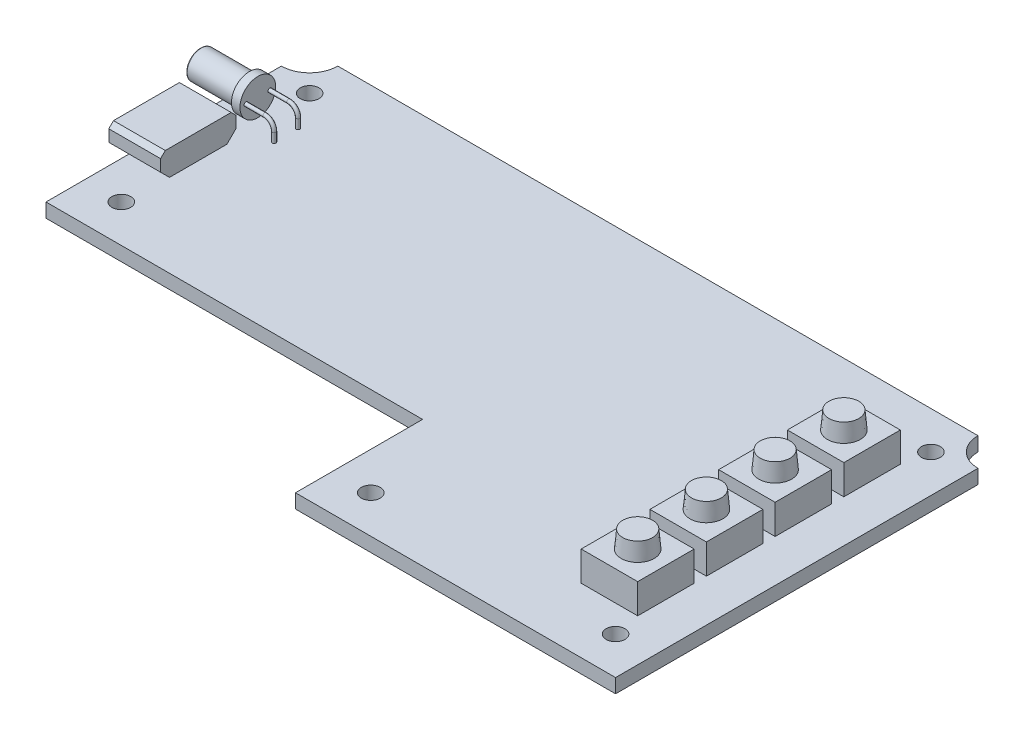
SolidWorks part; units mm, degrees
ref_plane "Front" through (0, 0, 0) normal (0, 0, 1) x (1, 0, 0)
ref_plane "Top" through (0, 0, 0) normal (0, 1, 0) x (1, 0, 0)
ref_plane "Right" through (0, 0, 0) normal (1, 0, 0) x (0, 0, -1)
sketch "Эскиз1" plane through (0, 0, 0) normal (0, 1, 0) x (1, 0, 0)
  line L0 (-37, -9) -> (3, -9)
  line L1 (37, -22.5) -> (-37, -22.5) construction
  line L2 (37, -22.5) -> (37, 19) construction
  line L3 (37, 19) -> (-37, 19) construction
  line L4 (-37, -22.5) -> (-37, 19) construction
  line L5 (0, -1.75) -> (0, 0) construction
  line L6 (-33, -18.5) -> (33, -18.5) construction
  line L7 (-33, -18.5) -> (-33, 15) construction
  line L8 (-33, 15) -> (33, 15) construction
  line L9 (33, -18.5) -> (33, 15) construction
  line L10 (-33, -18.5) -> (33, 15) construction
  line L11 (-33, 15) -> (33, -18.5) construction
  line L18 (37, -22.5) -> (-37, 19) construction
  line L19 (37, 19) -> (-37, -22.5) construction
  line L20 (3, -9) -> (3, -22.5)
  line L21 (-37, 19) -> (-37, -9) construction
  line L22 (3, -22.5) -> (37, -22.5)
  line L23 (37, -22.5) -> (37, 16)
  line L24 (34, 19) -> (-34, 19)
  line L25 (-37, 16) -> (-37, -9)
  line L26 (37, 19) -> (37, -22.5) construction
  line L27 (37, 19) -> (-37, 19) construction
  line L28 (-37, 19) -> (-37, -22.5) construction
  circle A0 centre (-33, -18.5) radius 1 construction
  circle A1 centre (-33, -5) radius 1
  circle A2 centre (33, -18.5) radius 1
  circle A3 centre (7, -18.5) radius 1
  circle A4 centre (-33, 15) radius 1
  arc A5 (-37, 16) -> (-34, 19) centre (-37, 19) ccw
  circle A6 centre (33, 15) radius 1
  arc A7 (37, 16) -> (34, 19) centre (37, 19) cw
  point P7 (0, -1.75)
  dimension "D4" = 74
  dimension "D5" = 41.5
  dimension "D6" = 28
  dimension "D7" = 40
  dimension "D9" = 2
  dimension "D10" = 3
  dimension "D11" = 3
  dimension "D1" = 1.75
  dimension "D2" = 33.5
  dimension "D3" = 66
  dimension "D8" = 20
  dimension "D12" = 26
extrude "Бобышка-Вытянуть1" add sketch "Эскиз1" along normal blind 1.5
sketch "Эскиз2" plane through (0, 1.5, 0) normal (0, 1, 0) x (1, 0, 0)
  line L1 (26.5, 11.5) -> (32.5, 11.5) construction
  line L2 (26.5, 11.5) -> (26.5, 7) construction
  line L3 (26.5, 7) -> (32.5, 7) construction
  line L4 (32.5, 11.5) -> (32.5, 7) construction
  line L5 (26.5, 11.5) -> (32.5, 7) construction
  line L6 (26.5, 7) -> (32.5, 11.5) construction
  line L8 (26.5, 4.2) -> (26.5, -0.3) construction
  line L9 (26.5, 4.2) -> (32.5, 4.2) construction
  line L10 (32.5, 4.2) -> (32.5, -0.3) construction
  line L11 (26.5, -0.3) -> (32.5, -0.3) construction
  line L12 (26.5, 4.2) -> (32.5, -0.3) construction
  line L13 (26.5, -0.3) -> (32.5, 4.2) construction
  line L14 (26.5, -3.1) -> (26.5, -7.6) construction
  line L15 (26.5, -3.1) -> (32.5, -3.1) construction
  line L16 (32.5, -3.1) -> (32.5, -7.6) construction
  line L17 (26.5, -7.6) -> (32.5, -7.6) construction
  line L18 (26.5, -3.1) -> (32.5, -7.6) construction
  line L19 (26.5, -7.6) -> (32.5, -3.1) construction
  line L20 (26.5, -10.4) -> (26.5, -14.9) construction
  line L21 (26.5, -10.4) -> (32.5, -10.4) construction
  line L22 (32.5, -10.4) -> (32.5, -14.9) construction
  line L23 (26.5, -14.9) -> (32.5, -14.9) construction
  line L24 (26.5, -10.4) -> (32.5, -14.9) construction
  line L25 (26.5, -14.9) -> (32.5, -10.4) construction
  line L26 (32.5, 4.95) -> (32.5, -1.05)
  line L27 (32.5, 12.25) -> (26.5, 12.25)
  line L28 (32.5, 12.25) -> (32.5, 6.25)
  line L29 (32.5, 6.25) -> (26.5, 6.25)
  line L30 (26.5, 12.25) -> (26.5, 6.25)
  line L31 (32.5, 12.25) -> (26.5, 6.25) construction
  line L32 (32.5, 6.25) -> (26.5, 12.25) construction
  line L33 (32.5, 4.95) -> (26.5, 4.95)
  line L34 (26.5, 4.95) -> (26.5, -1.05)
  line L35 (32.5, -1.05) -> (26.5, -1.05)
  line L36 (32.5, -2.35) -> (32.5, -8.35)
  line L37 (32.5, -2.35) -> (26.5, -2.35)
  line L38 (26.5, -2.35) -> (26.5, -8.35)
  line L39 (32.5, -8.35) -> (26.5, -8.35)
  line L40 (32.5, -9.65) -> (32.5, -15.65)
  line L41 (32.5, -9.65) -> (26.5, -9.65)
  line L42 (26.5, -9.65) -> (26.5, -15.65)
  line L43 (32.5, -15.65) -> (26.5, -15.65)
  line L44 (34, 19) -> (37, 19) construction
  line L45 (37, 19) -> (37, 16) construction
  line L46 (37, -22.5) -> (37, 16) construction
  line L47 (34, 19) -> (-34, 19) construction
  point P0 (29.5, 9.25)
  point P9 (29.5, 9.25)
  dimension "D1" = 4.5
  dimension "D2" = 6
  dimension "D3" = 7.5
  dimension "D4" = 4.5
  dimension "D6" = 6
  dimension "D7" = 6
  dimension "D8" = 4
  dimension "D5" = 4
extrude "Бобышка-Вытянуть2" add sketch "Эскиз2" along normal blind 3.15
sketch "Эскиз3" plane through (0, 4.65, 0) normal (0, 1, 0) x (1, 0, 0)
  line L0 (26.5, 12.25) -> (32.5, 6.25) construction
  line L1 (26.5, 4.95) -> (32.5, -1.05) construction
  line L2 (32.5, 12.25) -> (26.5, 6.25) construction
  line L3 (26.5, 4.95) -> (26.5, -1.05) construction
  line L4 (32.5, 4.95) -> (26.5, -1.05) construction
  line L5 (26.5, 4.95) -> (26.5, -1.05) construction
  line L6 (32.5, -8.35) -> (26.5, -2.35) construction
  line L7 (32.5, -2.35) -> (26.5, -8.35) construction
  line L8 (32.5, -2.35) -> (26.5, -2.35) construction
  line L9 (26.5, -2.35) -> (26.5, -8.35) construction
  line L10 (26.5, -9.65) -> (32.5, -15.65) construction
  line L11 (32.5, -9.65) -> (26.5, -15.65) construction
  circle A0 centre (29.5, 9.25) radius 1.75
  circle A1 centre (29.5, 1.95) radius 1.75
  circle A2 centre (29.5, -5.35) radius 1.75
  circle A3 centre (29.5, -12.65) radius 1.75
  dimension "D1" = 3.5
extrude "Бобышка-Вытянуть3" add sketch "Эскиз3" along normal blind 1.85 draft 5
sketch "Эскиз4" plane through (0, 1.5, 0) normal (0, 1, 0) x (1, 0, 0)
  line L0 (-27.2061, 19) -> (-27.2061, 2.87) construction
  line L2 (-27.2061, 2.87) -> (-37, 2.87) construction
  line L4 (-37, 16) -> (-37, 19) construction
  line L5 (-32.7, -1.13) -> (-38.2, -1.13)
  line L6 (-32.7, -1.13) -> (-32.7, 6.87)
  line L7 (-32.7, 6.87) -> (-38.2, 6.87)
  line L8 (-38.2, -1.13) -> (-38.2, 6.87)
  line L9 (-32.7, -1.13) -> (-38.2, 6.87) construction
  line L10 (-32.7, 6.87) -> (-38.2, -1.13) construction
  line L11 (-37, 19) -> (-34, 19) construction
  line L12 (-37, 16) -> (-37, -9) construction
  line L13 (34, 19) -> (-34, 19) construction
  point P4 (-35.45, 2.87)
  dimension "D1" = 16.13
  dimension "D2" = 1.2
  dimension "D3" = 5.5
  dimension "D4" = 8
extrude "Бобышка-Вытянуть4" add sketch "Эскиз4" along normal blind 2.4
sketch "Эскиз5" plane through (-38.2, 0, 0) normal (-1, 0, 0) x (0, 0, 1)
  line L0 (-6.87, 3.9) -> (1.13, 1.5) construction
  line L1 (1.13, 3.9) -> (1.13, 1.5) construction
  line L2 (-6.87, 1.5) -> (1.13, 1.5) construction
  line L3 (-6.87, 1.5) -> (1.13, 3.9) construction
  line L4 (-6.87, 3.9) -> (-6.87, 1.5) construction
  line L6 (1.13, 1.2) -> (-6.87, 1.2)
  line L7 (1.13, 1.2) -> (1.13, 4.2)
  line L8 (1.13, 4.2) -> (-6.87, 4.2)
  line L9 (-6.87, 1.2) -> (-6.87, 4.2)
  line L10 (1.13, 1.2) -> (-6.87, 4.2) construction
  line L11 (1.13, 4.2) -> (-6.87, 1.2) construction
  point P12 (-2.87, 2.7)
  dimension "D1" = 3
extrude "Бобышка-Вытянуть5" add sketch "Эскиз5" against normal up to surface (5.5 mm away) up to face at (-32.7, 2.7, -2.87)
chamfer "Фаска1" distance 0.5 angle 45 2 edges at (-35.45, 4.2, -6.87) (-35.45, 4.2, 1.13)
chamfer "Фаска2" distance 1.25 2 edges at (-37.6, 1.2, 1.13) (-37.6, 1.2, -6.87)
sketch "Эскиз6" plane through (0, 1.5, 0) normal (0, 1, 0) x (1, 0, 0)
  line L0 (-30.4, 19) -> (-30.4, 11.17) construction
  line L2 (-30.4, 11.17) -> (-37, 11.17) construction
  line L4 (-30.4, 11.17) -> (-30.4, 8.63) construction
  line L5 (34, 19) -> (-34, 19) construction
  line L6 (-37, 16) -> (-37, 5.92) construction
  circle A0 centre (-30.4, 11.17) radius 0.2
  circle A1 centre (-30.4, 8.63) radius 0.2
  dimension "D3" = 0.4
  dimension "D1" = 7.83
  dimension "D2" = 6.6
  dimension "D4" = 2.54
sketch "Эскиз7" plane through (0, 0, 0) normal (0, 0, 1) x (1, 0, 0)
  line L0 (-30.4, 1.5) -> (-30.4, 2.5)
  line L1 (-30.4, 1.5) -> (-37, 1.5) construction
  line L2 (-33.4, 3.5) -> (-31.4, 3.5)
  arc A0 (-30.4, 2.5) -> (-31.4, 3.5) centre (-31.4, 2.5) ccw
  dimension "D1" = 1
  dimension "D2" = 2
  dimension "D3" = 2
sweep "По траектории1" add profiles "Эскиз6" path "Эскиз7"
sketch "Эскиз8" plane through (-33.4, 0, 0) normal (-1, 0, 0) x (0, 0, 1)
  line L0 (-11.37, 3.5) -> (-8.43, 3.5) construction
  circle A0 centre (-9.9, 3.5) radius 1.9
  dimension "D1" = 3.8
extrude "Бобышка-Вытянуть6" add sketch "Эскиз8" along normal blind 0.9
sketch "Эскиз9" plane through (-34.3, 0, 0) normal (-1, 0, 0) x (0, 0, 1)
  line L0 (-16, 0) -> (9, 0) construction
  line L2 (-19, 1.5) -> (-19, 0) construction
  circle A0 centre (-9.9, 3.5) radius 1.5
  circle A1 centre (-9.9, 3.5) radius 1.9 construction
  dimension "D1" = 3
  dimension "D2" = 3.5
  dimension "D3" = 9.1
extrude "Бобышка-Вытянуть7" add sketch "Эскиз9" along normal blind 5.2
sketch "Эскиз16" plane through (-38.2, 0, 0) normal (-1, 0, 0) x (0, 0, 1)
  line L0 (-6.67, 3.6172) -> (-6.67, 2.5328)
  line L1 (-6.67, 2.5328) -> (-5.5372, 1.4)
  line L2 (-5.5372, 1.4) -> (-0.2028, 1.4)
  line L3 (-0.2028, 1.4) -> (0.93, 2.5328)
  line L4 (0.93, 2.5328) -> (0.93, 3.6172)
  line L5 (0.93, 3.6172) -> (0.5472, 4)
  line L6 (0.5472, 4) -> (-6.2872, 4)
  line L7 (-6.2872, 4) -> (-6.67, 3.6172)
  line L8 (-6.37, 4.2) -> (-6.87, 3.7) construction
  line L9 (-6.87, 3.7) -> (-6.87, 2.45) construction
  line L10 (-6.87, 2.45) -> (-5.62, 1.2) construction
  line L11 (-5.62, 1.2) -> (-0.12, 1.2) construction
  line L12 (-0.12, 1.2) -> (1.13, 2.45) construction
  line L13 (1.13, 3.7) -> (1.13, 2.45) construction
  line L14 (1.13, 3.7) -> (0.63, 4.2) construction
  line L15 (0.63, 4.2) -> (-6.37, 4.2) construction
  dimension "D1" = 0.2
  dimension "D2" = 0.2
  dimension "D3" = 0.2
  dimension "D4" = 0.2
  dimension "D5" = 0.2
  dimension "D6" = 0.2
  dimension "D7" = 0.2
  dimension "D8" = 0.2
extrude "Вырез-Вытянуть1" cut sketch "Эскиз16" against normal blind 4
sketch "Эскиз17" plane through (-34.2, 0, 0) normal (-1, 0, 0) x (0, 0, 1)
  line L0 (-6.67, 3.6172) -> (0.93, 2.5328) construction
  line L1 (0.93, 3.6172) -> (-6.67, 2.5328) construction
  line L2 (-6.27, 3.575) -> (-6.37, 3.475)
  line L3 (0.53, 2.575) -> (-6.27, 2.575)
  line L4 (0.63, 2.675) -> (0.63, 3.475)
  line L5 (0.53, 3.575) -> (-6.27, 3.575)
  line L6 (-6.37, 2.675) -> (-6.37, 3.475)
  line L7 (0.63, 2.575) -> (-6.37, 3.575) construction
  line L8 (0.63, 3.575) -> (-6.37, 2.575) construction
  line L9 (-6.27, 2.575) -> (-6.37, 2.675)
  line L10 (0.63, 3.475) -> (0.53, 3.575)
  line L11 (0.63, 2.675) -> (0.53, 2.575)
  point P8 (-2.87, 3.075)
  dimension "D1" = 1
  dimension "D2" = 7
extrude "Бобышка-Вытянуть8" add sketch "Эскиз17" along normal blind 3
fillet "Скругление1" radius 0.1 1 edges at (-39.5, 3.5, -8.4)
